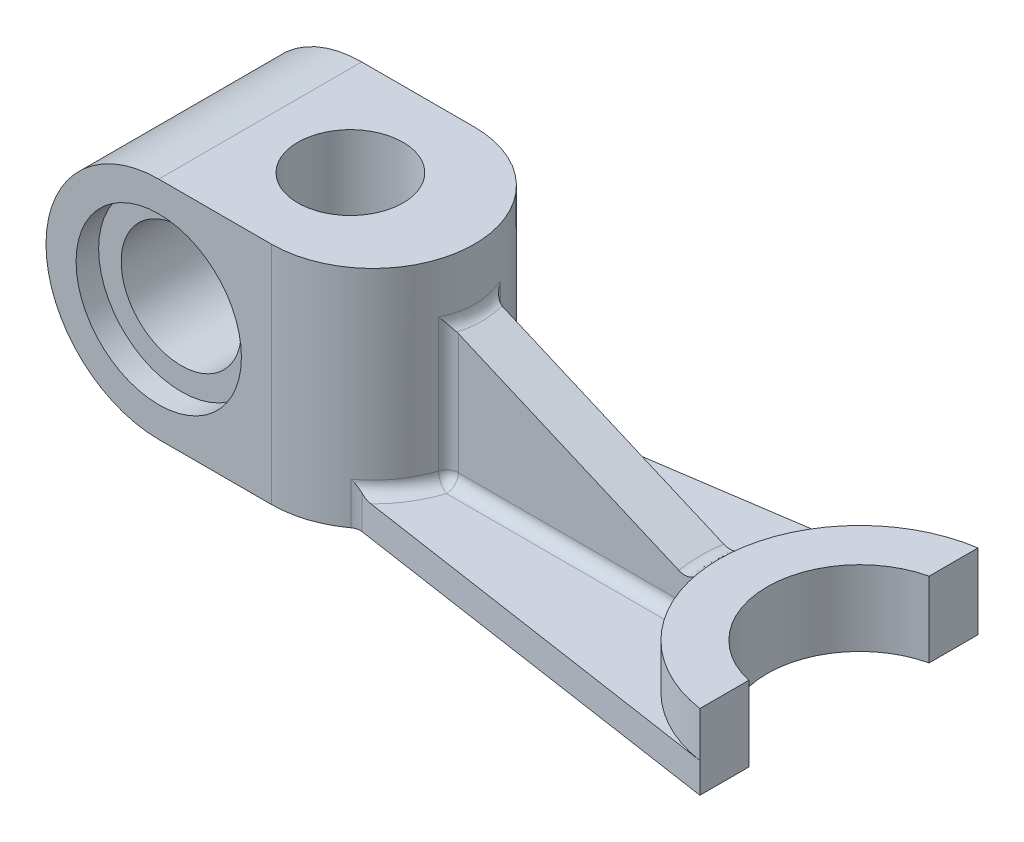
SolidWorks part; units mm, degrees
ref_plane "Front Plane" through (0, 0, 0) normal (0, 0, 1) x (1, 0, 0)
ref_plane "Top Plane" through (0, 0, 0) normal (0, 1, 0) x (1, 0, 0)
ref_plane "Right Plane" through (0, 0, 0) normal (1, 0, 0) x (0, 0, -1)
sketch "Sketch1" plane through (0, 0, 0) normal (0, 0, 1) x (1, 0, 0)
  line L0 (0, -23.8125) -> (23.8125, -23.8125)
  line L1 (23.8125, -23.8125) -> (23.8125, 23.8125)
  line L2 (23.8125, 23.8125) -> (0, 23.8125)
  circle A0 centre (0, 0) radius 23.8125
  dimension "D1" = 47.625
extrude "Boss-Extrude1" add sketch "Sketch1" along normal mid plane 42.8625 contours A0 | A0 L0 L1 | A0 L1 L2 region at (18.4936, -18.4936, 0) region at (0, 0, 0) region at (18.4936, 18.4936, 0)
sketch "Sketch2" plane through (0, 23.8125, 0) normal (0, 1, 0) x (1, 0, 0)
  line L0 (0, 0) -> (48.8911, 0) construction
  line L1 (0, -21.4312) -> (0, 21.4312) construction
  line L2 (23.8125, -21.4312) -> (0, -21.4312) construction
  line L3 (23.8125, 21.4312) -> (0, 21.4312) construction
  line L4 (23.8125, 21.4312) -> (23.8125, -21.4312)
  line L8 (23.8125, 21.4312) -> (0, 21.4312)
  line L9 (0, 21.4312) -> (0, -21.4312)
  line L10 (0, -21.4312) -> (23.8125, -21.4312)
  line L11 (23.8125, -21.4312) -> (23.8125, 21.4312)
  line L12 (23.8125, 21.4312) -> (0, 21.4312)
  line L13 (0, 21.4312) -> (0, -21.4312)
  line L14 (0, -21.4312) -> (23.8125, -21.4312)
  arc A0 (23.8125, 21.4312) -> (23.8125, -21.4312) centre (23.8125, 0) cw
  line M8 (23.8125, -21.4312) -> (23.8125, 21.4312)
  dimension "D1" = 0
extrude "Boss-Extrude2" add sketch "Sketch2" against normal blind 47.625 contours L0 A0 M8 | L4 L0 A0 region at (32.9082, 23.8125, -9.0957) region at (32.9082, 23.8125, 9.0957)
sketch "Sketch5" plane through (0, 0, 21.4312) normal (0, 0, 1) x (1, 0, 0)
  line L0 (0, 23.8125) -> (0, -23.8125) construction
  arc A0 (0, 23.8125) -> (0, -23.8125) centre (0, 0) ccw construction
hole_wizard "CBORE for #00 Binding Head Machine Screw2" positions "3DSketch1" profile "Sketch6" counterbore size "#00" standard "ANSI Inch" end condition through all
sketch3d "3DSketch1"
  line L0 (0, 23.8125, 21.4312) -> (0, -23.8125, 21.4312) construction
  point P0 (0, 0, 0)
  point P3 (0, 0, 0)
  point P6 (0, 0, 21.4313)
  point P10 (0, 0, 21.4313)
  point P12 (0, 0, 21.4312)
sketch "Sketch6" plane through (0, 0, 21.4313) normal (1, 0, 0) x (0, -1, 0)
  line L0 (0, 0) -> (0, 42.8625)
  line L1 (0, 42.8625) -> (12.7, 42.8625)
  line L3 (12.7, 42.8625) -> (12.7, 4.7625)
  line L4 (12.7, 4.7625) -> (17.4625, 4.7625)
  line L5 (17.4625, 4.7625) -> (17.4625, 0)
  line L7 (17.4625, 0) -> (0, 0)
  line L11 (0, -6.35) -> (0, 107.95) construction
  dimension "Thru Hole Dia." = 25.4
  dimension "Thru Hole Depth" = 42.8625
  dimension "C'Bore Dia." = 34.925
  dimension "C'Bore Depth" = 4.7625
sketch "Sketch8" plane through (0, -23.8125, 0) normal (0, -1, 0) x (1, 0, 0)
  line L0 (0, 0) -> (122.2375, 0) construction
  line L1 (-23.8125, 21.4312) -> (-23.8125, -21.4312) construction
  line L2 (122.2375, 29.3687) -> (122.2375, 19.05)
  line L3 (122.2375, -19.05) -> (122.2375, -29.3687)
  line L4 (122.2375, 29.3687) -> (122.2375, -29.3687) construction
  line L5 (122.2375, -29.3687) -> (37.2829, -16.6687)
  line L6 (122.2375, 29.3687) -> (37.2829, 16.6687)
  line L7 (0, 21.4312) -> (0, -21.4312) construction
  arc A0 (122.2375, 19.05) -> (122.2375, -19.05) centre (126.6279, 0) ccw
  arc A1 (122.2375, 29.3687) -> (122.2375, -29.3687) centre (126.6279, 0) ccw
  circle A2 centre (19.05, 0) radius 11.1125
  arc A3 (23.8125, -21.4312) -> (23.8125, 21.4312) centre (23.8125, 0) ccw construction
  point P14 (107.0785, 0)
  dimension "D3" = 58.7375
  dimension "D4" = 19.05
  dimension "D6" = 22.225
  dimension "D1" = 38.1
  dimension "D2" = 146.05
  dimension "D5" = 16.6687
sketch "Sketch9" plane through (0, -23.8125, 0) normal (0, -1, 0) x (1, 0, 0)
  circle A0 centre (19.05, 0) radius 11.1125 construction
  circle A1 centre (19.05, 0) radius 11.1125
extrude "Cut-Extrude2" cut sketch "Sketch9" against normal through all
extrude "Boss-Extrude4" add sketch "Sketch8" against normal blind 15.875 separate body contours L2 A1 L3 A0 region at (121.5979, -23.8125, 24.2094)
sketch "Sketch11" plane through (0, -23.8125, 0) normal (0, -1, 0) x (1, 0, 0)
  line L0 (122.2375, -29.3687) -> (37.2829, -16.6687) construction
  line L1 (122.2375, 29.3688) -> (37.2829, 16.6687) construction
  line L2 (122.2375, -29.3687) -> (37.2829, -16.6687)
  line L3 (122.2375, 29.3688) -> (37.2829, 16.6687)
  arc A0 (23.8125, -21.4312) -> (23.8125, 21.4312) centre (23.8125, 0) ccw construction
  arc A1 (122.2375, 29.3688) -> (122.2375, -29.3687) centre (126.6279, 0) ccw construction
  arc A2 (37.2829, -16.6687) -> (37.2829, 16.6687) centre (23.8125, 0) ccw
  arc A3 (122.2375, 29.3688) -> (122.2375, -29.3687) centre (126.6279, 0) ccw
extrude "Boss-Extrude5" add sketch "Sketch11" against normal blind 6.35
sketch "Sketch12" plane through (0, 0, 0) normal (0, 0, 1) x (1, 0, 0)
  line L0 (45.2437, 11.1125) -> (96.9328, -11.1125)
  line L4 (122.2375, -7.9375) -> (96.9328, -7.9375) construction
  line L13 (45.2437, -17.4625) -> (45.2437, 23.8125) construction
  line L14 (45.2437, 23.8125) -> (23.8125, 23.8125) construction
  point P2 (96.9328, -11.1125)
  point P4 (0, 0)
  point P5 (0, 0)
  point P9 (45.2437, 11.1125)
  point P10 (0, 0)
  dimension "D1" = 3.175
  dimension "D2" = 12.7
  dimension "D3" = 96.9328
rib "Rib2" sketch "Sketch12" sketch "Sketch12" thickness 9.525 extrusion direction parallel to sketch draft on no parameters "D1"=9.525
fillet "Fillet1" radius 2.54 9 edges at (71.0125, -17.4625, 4.7625) (71.0125, -17.4625, -4.7625) (41.9974, -17.4625, -11.3405) (37.2829, -20.6375, -16.6687) (41.9974, -17.4625, 11.3405) (37.2829, -20.6375, 16.6688) (44.7079, -3.0598, -4.7625) (44.7079, -3.0598, 4.7625) (45.2437, 11.1125, 0)
fillet "Fillet2" radius 3.175 1 edges at (96.9328, -11.1125, 0)
